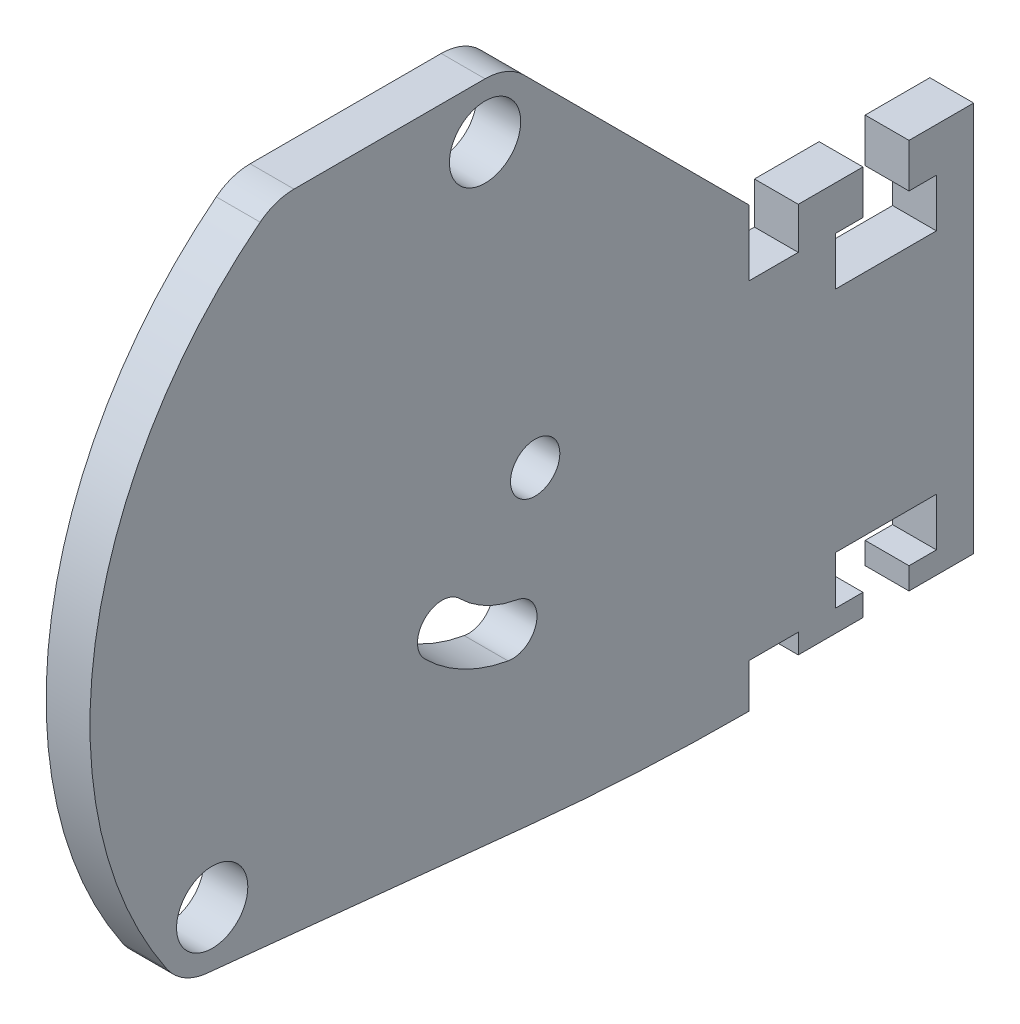
SolidWorks part; units mm, degrees
ref_plane "Front Plane" through (0, 0, 0) normal (0, 0, 1) x (1, 0, 0)
ref_plane "Top Plane" through (0, 0, 0) normal (0, 1, 0) x (1, 0, 0)
ref_plane "Right Plane" through (0, 0, 0) normal (1, 0, 0) x (0, 0, -1)
sketch "Sketch1" plane through (0, 0, 0) normal (1, 0, 0) x (0, 0, -1)
  line L0 (-16, 7.5) -> (20, 7.5) construction
  line L1 (-16, 15) -> (20, 15)
  line L2 (-16, 15) -> (-16, 0)
  line L3 (-16, 0) -> (20, 0)
  line L4 (20, 15) -> (20, 0)
  line L5 (0, 15) -> (0, 0) construction
  line L10 (0, 12.5) -> (-4.2426, 8.2574) construction
  line L11 (9.75, 15) -> (9.75, 18)
  line L12 (9.75, 18) -> (-4.5399, 32.2899)
  line L13 (20, 15) -> (12, 15)
  line L14 (20, 15) -> (20, 16.9)
  line L15 (20, 16.9) -> (12, 16.9)
  line L16 (12, 15) -> (12, 16.9)
  line L18 (16, 16.9) -> (16, -0.9) construction
  line L19 (20, 0) -> (12, 0)
  line L20 (20, 0) -> (20, -0.9)
  line L21 (20, -0.9) -> (12, -0.9)
  line L22 (12, 0) -> (12, -0.9)
  line L23 (14.95, 0.1) -> (17.05, 0.1)
  line L24 (14.95, 14.9) -> (17.05, 14.9)
  line L25 (14.95, 14.9) -> (14.95, 16.9)
  line L26 (14.95, 16.9) -> (17.05, 16.9)
  line L27 (17.05, 14.9) -> (17.05, 16.9)
  line L28 (14.95, 14.9) -> (17.05, 16.9) construction
  line L29 (14.95, 16.9) -> (17.05, 14.9) construction
  line L30 (13.7, 12.7) -> (18.3, 12.7)
  line L31 (13.7, 12.7) -> (13.7, 14.9)
  line L32 (13.7, 14.9) -> (18.3, 14.9)
  line L33 (18.3, 12.7) -> (18.3, 14.9)
  line L34 (13.7, 12.7) -> (18.3, 14.9) construction
  line L35 (13.7, 14.9) -> (18.3, 12.7) construction
  line L36 (14.95, 0.1) -> (14.95, -1.9)
  line L37 (14.95, -1.9) -> (17.05, -1.9)
  line L38 (17.05, 0.1) -> (17.05, -1.9)
  line L39 (13.7, 2.3) -> (13.7, 0.1)
  line L40 (13.7, 0.1) -> (18.3, 0.1)
  line L41 (18.3, 2.3) -> (18.3, 0.1)
  line L42 (13.7, 2.3) -> (18.3, 2.3)
  line L43 (-1.25, 29) -> (-11.8322, 29)
  line L44 (0, 12.5) -> (-1.2372, 5.4832) construction
  line L45 (4.75, -2) -> (-14.9839, 0.0129)
  line L46 (9.75, 0) -> (4.75, 0)
  line L47 (9.75, 0) -> (9.75, -2)
  line L48 (9.75, -2) -> (4.75, -2)
  line L49 (4.75, 0) -> (4.75, -2)
  circle A2 centre (0, 12.5) radius 1.125
  circle A12 centre (-4.2426, 8.2574) radius 1.125
  circle A14 centre (0, 12.5) radius 20.3039
  circle A15 centre (0, 12.5) radius 4.875
  circle A16 centre (0, 12.5) radius 7.125
  circle A17 centre (-14.7303, 2.5) radius 2.5
  circle A18 centre (-14.7303, 2.5) radius 1.625
  circle A19 centre (-2.2855, 26.5) radius 2.5
  circle A20 centre (-2.2855, 26.5) radius 1.625
  circle A21 centre (-10.9991, 26.5) radius 2.5
  circle A22 centre (-1.0419, 6.5912) radius 1.125
  point P15 (16, 15.9)
  point P34 (16, 13.8)
  dimension "D1" = 2.25
  dimension "D2" = 5
  dimension "D7" = 6
  dimension "D11" = 2.1
  dimension "D16" = 5
  dimension "D17" = 3.25
  dimension "D3" = 15
  dimension "D4" = 20
  dimension "D5" = 16
  dimension "D6" = 45
  dimension "D8" = 2.25
  dimension "D9" = 1.9
  dimension "D10" = 8
  dimension "D12" = 2
  dimension "D13" = 2.2
  dimension "D14" = 4.6
  dimension "D15" = 3
  dimension "D18" = 14
  dimension "D19" = 10
  dimension "D20" = 0.9
  dimension "D21" = 2
  dimension "D22" = 5
extrude "Boss-Extrude1" add sketch "Sketch1" along normal blind 2 contours A16 L1 L11 L12 A14 L2 | A16 L1 L2 L3 L36 L40 L39 L42 L41 A14 L4 L27 L32 L33 L30 L31 L25 | L1 A16 A15 | L1 A16 A12 A15 | L1 A15 A2 | L1 A15 | A16 L1 A15 | A14 L38 L3 L4 L41 L40 | L3 L38 L21 L20 | L36 L3 L22 L21 | L1 L25 L15 L16 | L27 L1 L14 L15 | A18 L2 A17 | A18 L2 A17 | A19 A20 | A21 | A14 L14 L15 | L3 L49 L48 L47 | L49 L3 L45 region at (0, 14.61, -10.875) region at (0, 19.0585, 8.5011) region at (0, 15.95, -13.475) region at (0, 9.6923, -4.2211) region at (0, 15.1412, -5.4286) region at (0, 13.7642, -4.5815) region at (0, 15.9731, 0) region at (0, 11.886, 5.7256) region at (0, 27.4296, 0.0412) region at (0, 15.9408, -18.5052) region at (0, 4.6164, 13.5212) region at (0, 2.5, 16.5586) region at (0, 26.5, 10.9991) region at (0, 3.0965, -19.1953) region at (0, 16.6061, -19.9416) region at (0, -0.45, -18.525) region at (0, -0.6667, 1.7858) region at (0, -1, -7.25) region at (0, -0.45, -13.475)
fillet "Fillet1" radius 100 1 edges at (1, -2, -4.75)
